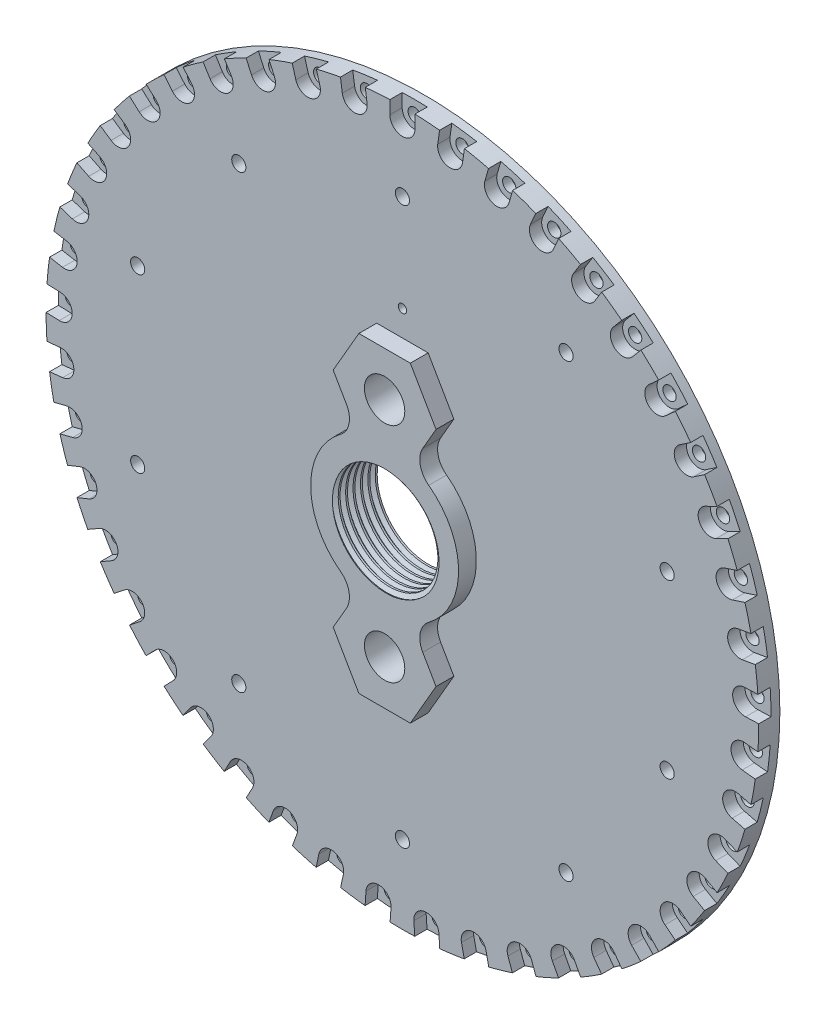
SolidWorks part; units mm, degrees
material "AISI 316 Stainless Steel Sheet (SS)"
ref_plane "Front Plane" through (0, 0, 0) normal (0, 0, 1) x (1, 0, 0)
ref_plane "Top Plane" through (0, 0, 0) normal (0, 1, 0) x (1, 0, 0)
ref_plane "Right Plane" through (0, 0, 0) normal (1, 0, 0) x (0, 0, -1)
sketch "Sketch1" plane through (0, 0, 0) normal (1, 0, 0) x (0, 0, -1)
  line L0 (0, 21.082) -> (0, 101.6)
  line L1 (0, 101.6) -> (6.0325, 101.6)
  line L2 (6.0325, 101.6) -> (6.0325, 95.25)
  line L4 (5.08, 95.25) -> (5.08, 56.8325)
  line L5 (5.08, 56.8325) -> (7.62, 56.8325)
  line L6 (7.62, 56.8325) -> (7.62, 53.0225)
  line L7 (7.62, 14.732) -> (-5.08, 14.732)
  line L8 (-5.08, 14.732) -> (-5.08, 21.082)
  line L9 (-5.08, 21.082) -> (0, 21.082)
  line L10 (0, 0) -> (59.2702, 0) construction
  line L12 (7.62, 49.6951) -> (6.2992, 49.6951)
  line L14 (7.62, 47.0535) -> (6.2992, 47.0535)
  line L15 (6.2992, 49.6951) -> (6.2992, 47.0535)
  line L20 (7.62, 47.0535) -> (7.62, 46.0375)
  line L22 (7.62, 50.4825) -> (7.62, 49.6951)
  line L23 (7.62, 21.59) -> (7.62, 14.732)
  line L24 (7.62, 46.0375) -> (5.08, 46.0375)
  line L26 (7.62, 21.59) -> (5.08, 21.59)
  line L27 (5.08, 46.0375) -> (5.08, 21.59)
  line L28 (7.62, 53.0225) -> (6.35, 53.0225)
  line L29 (6.0325, 95.25) -> (5.08, 95.25)
  line L32 (7.62, 50.4825) -> (6.35, 50.4825)
  line L33 (6.35, 53.0225) -> (6.35, 50.4825)
  point P19 (6.35, 51.7525)
  point P22 (6.2992, 48.3743)
  dimension "D1" = 203.2
  dimension "D6" = 12.7
  dimension "D8" = 6.35
  dimension "D10" = 96.7486
  dimension "D9" = 2.6416
  dimension "D11" = 1.3208
  dimension "D7" = 29.464
  dimension "D4" = 2.54
  dimension "D14" = 43.18
  dimension "D2" = 2.54
  dimension "D3" = 7.62
  dimension "D5" = 113.665
  dimension "D13" = 92.075
  dimension "D15" = 1.27
  dimension "D16" = 2.54
  dimension "D17" = 103.505
  dimension "D12" = 1.5875
  dimension "D18" = 6.35
revolve "Revolve1" add sketch "Sketch1" angle 360 about L10 region at (0, 54.5313, -2.5312)
thread "Thread1" pitch 2.1167 method cut profile "Thread Profile1" start angle 0, offset 4.318, length 0, pitch 2.1167, diameter 29.464
ref_plane "Plane1" through (-14.732, 0, 9.398) normal (0, -1, 0) x (-1, 0, 0)
sketch "Thread Profile1" plane through (-14.732, 0, 9.398) normal (0, -1, 0) x (-1, 0, 0)
  line L0 (0, 0) -> (0, 2.1167) construction
  line L1 (0, 0) -> (1.1457, 0.6615)
  line L2 (1.1457, 0.6615) -> (1.1457, 0.926)
  line L3 (1.1457, 0.926) -> (0, 1.5875)
  line L4 (1.1457, 0.7937) -> (0, 0.7937) construction
  line L11 (0, 0) -> (0, 1.5875)
  point P2 (0, 0)
  dimension "Pitch" = 2.1167
  dimension "Profile_Angle" = 60
  dimension "Profile_Land" = 0.2646
  dimension "Profile_Height" = 1.1457
sketch "Sketch15" plane through (0, 0, 0) normal (0, 0, 1) x (1, 0, 0)
  line L10 (0, 0) -> (104.8126, 0) construction
  line L11 (7.3323, 19.05) -> (14.6647, 31.75)
  line L12 (14.6647, 31.75) -> (7.3323, 44.45)
  line L13 (7.3323, 44.45) -> (-7.3323, 44.45)
  line L14 (-7.3323, 44.45) -> (-14.6647, 31.75)
  line L15 (-14.6647, 31.75) -> (-7.3323, 19.05)
  line L16 (-7.3323, 19.05) -> (7.3323, 19.05)
  line L17 (-7.3323, -19.05) -> (7.3323, -19.05)
  line L18 (-14.6647, -31.75) -> (-7.3323, -19.05)
  line L19 (-7.3323, -44.45) -> (-14.6647, -31.75)
  line L20 (7.3323, -44.45) -> (-7.3323, -44.45)
  line L21 (14.6647, -31.75) -> (7.3323, -44.45)
  line L22 (7.3323, -19.05) -> (14.6647, -31.75)
  circle A8 centre (0, 31.75) radius 12.7 construction
  circle A9 centre (0, -31.75) radius 12.7 construction
  dimension "D2" = 63.5
  dimension "D1" = 25.4
extrude "Boss-Extrude1" add sketch "Sketch15" along normal up to surface (5.08 mm away) up to face at (21.082, 0, 5.08)
hole_wizard "1/2-20 Tapped Hole2" positions "Sketch20" profile "Sketch17" tap size "1/2-20" standard "ANSI Inch" end condition through all
sketch "Sketch20" plane through (0, 0, 5.08) normal (0, 0, 1) x (1, 0, 0)
  point P9 (0, 31.75)
  point P16 (0, -31.75)
sketch "Sketch17" plane through (0, 31.75, 5.08) normal (1, 0, 0) x (0, -1, 0)
  line L0 (0, 0) -> (0, 13.4424)
  line L1 (0, 13.4424) -> (5.7544, 13.4424)
  line L2 (5.7544, 13.4424) -> (5.7544, 0)
  line L5 (5.7544, 0) -> (0, 0)
  line L11 (0, -6.35) -> (0, 107.95) construction
  dimension "Thru Tap Drill Dia." = 11.5087
  dimension "Thru Tap Drill Depth" = 13.4424
cosmetic thread "Hole Thread3" parameters "D2"=12.7
cosmetic thread "Hole Thread4" parameters "D2"=12.7
hole_wizard "CBORE for #6 Socket Head Cap Screw1" positions "Sketch31" profile "Sketch9" counterbore size "#6" standard "ANSI Inch" end condition up to next
sketch "Sketch31" [suppressed] plane through (0, 0, 0) normal (0, 0, 1) x (1, 0, 0)
  circle A0 centre (0, 0) radius 97.79 construction
  point P0 (0, 97.79)
  point P16 (13.6097, 96.8383)
  point P17 (26.9546, 94.0018)
  point P18 (39.7748, 89.3356)
  point P19 (51.8208, 82.9306)
  point P20 (62.8582, 74.9115)
  point P21 (72.6721, 65.4343)
  point P22 (81.0716, 54.6835)
  point P23 (87.8931, 42.8683)
  point P24 (93.0038, 30.2188)
  point P25 (96.3044, 16.9811)
  point P26 (97.7304, 3.4128)
  point P27 (97.2543, -10.2218)
  point P28 (94.8852, -23.6575)
  point P29 (90.6693, -36.6328)
  point P30 (84.6886, -48.895)
  point P31 (77.0596, -60.2055)
  point P32 (67.9306, -70.3442)
  point P33 (57.4795, -79.1138)
  point P34 (45.9096, -86.3434)
  point P35 (33.4461, -91.8925)
  point P36 (20.3317, -95.6531)
  point P37 (6.8215, -97.5518)
  point P38 (-6.8215, -97.5518)
  point P39 (-20.3317, -95.6531)
  point P40 (-33.4461, -91.8925)
  point P41 (-45.9096, -86.3434)
  point P42 (-57.4795, -79.1138)
  point P43 (-67.9306, -70.3442)
  point P44 (-77.0596, -60.2055)
  point P45 (-84.6886, -48.895)
  point P46 (-90.6693, -36.6328)
  point P47 (-94.8852, -23.6575)
  point P48 (-97.2543, -10.2218)
  point P49 (-97.7304, 3.4128)
  point P50 (-96.3044, 16.9811)
  point P51 (-93.0038, 30.2188)
  point P52 (-87.8931, 42.8683)
  point P53 (-81.0716, 54.6835)
  point P54 (-72.6721, 65.4343)
  point P55 (-62.8582, 74.9115)
  point P56 (-51.8208, 82.9306)
  point P57 (-39.7748, 89.3356)
  point P58 (-26.9546, 94.0018)
  point P59 (-13.6097, 96.8383)
  dimension "D1" = 195.58
  dimension "D2" = 45
sketch "Sketch9" plane through (0, 97.79, 0) normal (1, 0, 0) x (0, -1, 0)
  line L0 (0, 0) -> (0, 6.0325)
  line L1 (0, 6.0325) -> (1.8986, 6.0325)
  line L3 (1.8986, 6.0325) -> (1.8986, 3.5052)
  line L4 (1.8986, 3.5052) -> (3.5725, 3.5052)
  line L5 (3.5725, 3.5052) -> (3.5725, 0)
  line L7 (3.5725, 0) -> (0, 0)
  line L11 (0, -6.35) -> (0, 107.95) construction
  dimension "Thru Hole Dia." = 3.7973
  dimension "Thru Hole Depth" = 6.0325
  dimension "C'Bore Dia." = 7.145
  dimension "C'Bore Depth" = 3.5052
sketch "Sketch29" plane through (0, 0, 0) normal (0, 0, 1) x (1, 0, 0)
  line L0 (3.5725, 97.79) -> (3.5725, 101.5372)
  line L1 (-3.5725, 97.79) -> (-3.5725, 101.5372)
  line L2 (17.1475, 96.3411) -> (17.669, 100.0518)
  line L3 (10.072, 97.3355) -> (10.5935, 101.0462)
  line L4 (30.3887, 93.0171) -> (31.4216, 96.6191)
  line L5 (23.5205, 94.9865) -> (24.5533, 98.5885)
  line L6 (43.0384, 87.8825) -> (44.5625, 91.3058)
  line L7 (36.5111, 90.7887) -> (38.0352, 94.2119)
  line L8 (54.8505, 81.0375) -> (56.8362, 84.2153)
  line L9 (48.7911, 84.8238) -> (50.7768, 88.0015)
  line L10 (65.5949, 72.6151) -> (68.0035, 75.4856)
  line L11 (60.1215, 77.2079) -> (62.5301, 80.0784)
  line L12 (75.0626, 62.7794) -> (77.8473, 65.2867)
  line L13 (70.2817, 68.0892) -> (73.0663, 70.5965)
  line L14 (83.0693, 51.7217) -> (86.1759, 53.8171)
  line L15 (79.0739, 57.6452) -> (82.1804, 59.7406)
  line L16 (89.4592, 39.6574) -> (92.8271, 41.3)
  line L17 (86.327, 46.0793) -> (89.6949, 47.7219)
  line L18 (94.1078, 26.8211) -> (97.6716, 27.9791)
  line L19 (91.8999, 33.6164) -> (95.4636, 34.7744)
  line L20 (96.9247, 13.4628) -> (100.615, 14.1135)
  line L21 (95.684, 20.4993) -> (99.3742, 21.15)
  line L22 (97.8551, -0.1575) -> (101.6, -0.0267)
  line L23 (97.6058, 6.9832) -> (101.3506, 7.1139)
  line L24 (96.8809, -13.7748) -> (100.6075, -14.1665)
  line L25 (97.6277, -6.6689) -> (101.3544, -7.0606)
  line L26 (94.021, -27.1239) -> (97.6568, -28.0305)
  line L27 (95.7495, -20.1912) -> (99.3854, -21.0977)
  line L28 (89.331, -39.9452) -> (92.8053, -41.3489)
  line L29 (92.0076, -33.3204) -> (95.4819, -34.7241)
  line L30 (82.9024, -51.9889) -> (86.1475, -53.8625)
  line L31 (86.4749, -45.8011) -> (89.72, -47.6747)
  line L32 (74.8601, -63.0207) -> (77.8129, -65.3277)
  line L33 (79.259, -57.3904) -> (82.2118, -59.6973)
  line L34 (65.3608, -72.8259) -> (67.9638, -75.5214)
  line L35 (70.5005, -67.8626) -> (73.1035, -70.5581)
  line L36 (54.5893, -81.2136) -> (56.7918, -84.2452)
  line L37 (60.3697, -77.0139) -> (62.5723, -80.0454)
  line L38 (42.7553, -88.0206) -> (44.5145, -91.3292)
  line L39 (49.064, -84.6663) -> (50.8232, -87.9748)
  line L40 (30.0891, -93.1144) -> (31.3707, -96.6356)
  line L41 (36.8032, -90.6707) -> (38.0848, -94.1919)
  line L42 (16.8372, -96.3958) -> (17.6163, -100.0611)
  line L43 (23.8261, -94.9103) -> (24.6052, -98.5756)
  line L44 (3.2577, -97.801) -> (3.5191, -101.539)
  line L45 (10.3853, -97.3026) -> (10.6467, -101.0406)
  line L46 (-10.3853, -97.3026) -> (-10.6467, -101.0406)
  line L47 (-3.2577, -97.801) -> (-3.5191, -101.539)
  line L48 (-23.8261, -94.9103) -> (-24.6052, -98.5756)
  line L49 (-16.8372, -96.3958) -> (-17.6163, -100.0611)
  line L50 (-36.8032, -90.6707) -> (-38.0848, -94.1919)
  line L51 (-30.0891, -93.1144) -> (-31.3707, -96.6356)
  line L52 (-49.064, -84.6663) -> (-50.8232, -87.9748)
  line L53 (-42.7553, -88.0206) -> (-44.5145, -91.3292)
  line L54 (-60.3697, -77.0139) -> (-62.5723, -80.0454)
  line L55 (-54.5893, -81.2136) -> (-56.7918, -84.2452)
  line L56 (-70.5005, -67.8626) -> (-73.1035, -70.5581)
  line L57 (-65.3608, -72.8259) -> (-67.9638, -75.5214)
  line L58 (-79.259, -57.3904) -> (-82.2118, -59.6973)
  line L59 (-74.8601, -63.0207) -> (-77.8129, -65.3277)
  line L60 (-86.4749, -45.8011) -> (-89.72, -47.6747)
  line L61 (-82.9024, -51.9889) -> (-86.1475, -53.8625)
  line L62 (-92.0076, -33.3204) -> (-95.4819, -34.7241)
  line L63 (-89.331, -39.9452) -> (-92.8053, -41.3489)
  line L64 (-95.7495, -20.1912) -> (-99.3854, -21.0977)
  line L65 (-94.021, -27.1239) -> (-97.6568, -28.0305)
  line L66 (-97.6277, -6.6689) -> (-101.3544, -7.0606)
  line L67 (-96.8809, -13.7748) -> (-100.6075, -14.1665)
  line L68 (-97.6058, 6.9832) -> (-101.3506, 7.1139)
  line L69 (-97.8551, -0.1575) -> (-101.6, -0.0267)
  line L70 (-95.684, 20.4993) -> (-99.3742, 21.15)
  line L71 (-96.9247, 13.4628) -> (-100.615, 14.1135)
  line L72 (-91.8999, 33.6164) -> (-95.4636, 34.7744)
  line L73 (-94.1078, 26.8211) -> (-97.6716, 27.9791)
  line L74 (-86.327, 46.0793) -> (-89.6949, 47.7219)
  line L75 (-89.4592, 39.6574) -> (-92.8271, 41.3)
  line L76 (-79.0739, 57.6452) -> (-82.1804, 59.7406)
  line L77 (-83.0693, 51.7217) -> (-86.1759, 53.8171)
  line L78 (-70.2817, 68.0892) -> (-73.0663, 70.5965)
  line L79 (-75.0626, 62.7794) -> (-77.8473, 65.2867)
  line L80 (-60.1215, 77.2079) -> (-62.5301, 80.0784)
  line L81 (-65.5949, 72.6151) -> (-68.0035, 75.4856)
  line L82 (-48.7911, 84.8238) -> (-50.7768, 88.0015)
  line L83 (-54.8505, 81.0375) -> (-56.8362, 84.2153)
  line L84 (-36.5111, 90.7887) -> (-38.0352, 94.2119)
  line L85 (-43.0384, 87.8825) -> (-44.5625, 91.3058)
  line L86 (-23.5205, 94.9865) -> (-24.5533, 98.5885)
  line L87 (-30.3887, 93.0171) -> (-31.4216, 96.6191)
  line L88 (-10.072, 97.3355) -> (-10.5935, 101.0462)
  line L89 (-17.1475, 96.3411) -> (-17.669, 100.0518)
  circle A0 centre (0, 97.79) radius 3.5725 construction
  circle A1 centre (0, 0) radius 101.6 construction
  circle A2 centre (13.6097, 96.8383) radius 3.5725
  circle A3 centre (0, 97.79) radius 3.5725
  circle A4 centre (26.9546, 94.0018) radius 3.5725
  circle A5 centre (0, 0) radius 101.6
  circle A7 centre (39.7748, 89.3356) radius 3.5725
  circle A8 centre (51.8208, 82.9306) radius 3.5725
  circle A9 centre (62.8582, 74.9115) radius 3.5725
  circle A10 centre (72.6721, 65.4343) radius 3.5725
  circle A11 centre (81.0716, 54.6835) radius 3.5725
  circle A12 centre (87.8931, 42.8683) radius 3.5725
  circle A13 centre (93.0038, 30.2188) radius 3.5725
  circle A14 centre (96.3044, 16.9811) radius 3.5725
  circle A15 centre (97.7304, 3.4128) radius 3.5725
  circle A16 centre (97.2543, -10.2218) radius 3.5725
  circle A17 centre (94.8852, -23.6575) radius 3.5725
  circle A18 centre (90.6693, -36.6328) radius 3.5725
  circle A19 centre (84.6886, -48.895) radius 3.5725
  circle A20 centre (77.0596, -60.2055) radius 3.5725
  circle A21 centre (67.9306, -70.3442) radius 3.5725
  circle A22 centre (57.4795, -79.1138) radius 3.5725
  circle A23 centre (45.9096, -86.3434) radius 3.5725
  circle A24 centre (33.4461, -91.8925) radius 3.5725
  circle A25 centre (13.6097, 96.8383) radius 1.8986 construction
  circle A26 centre (20.3317, -95.6531) radius 3.5725
  circle A27 centre (6.8215, -97.5518) radius 3.5725
  circle A28 centre (-6.8215, -97.5518) radius 3.5725
  circle A29 centre (-20.3317, -95.6531) radius 3.5725
  circle A30 centre (-33.4461, -91.8925) radius 3.5725
  circle A31 centre (-45.9096, -86.3434) radius 3.5725
  circle A32 centre (-57.4795, -79.1138) radius 3.5725
  circle A33 centre (-67.9306, -70.3442) radius 3.5725
  circle A34 centre (-77.0596, -60.2055) radius 3.5725
  circle A35 centre (-84.6886, -48.895) radius 3.5725
  circle A36 centre (-90.6693, -36.6328) radius 3.5725
  circle A37 centre (-94.8852, -23.6575) radius 3.5725
  circle A38 centre (-97.2543, -10.2218) radius 3.5725
  circle A39 centre (-97.7304, 3.4128) radius 3.5725
  circle A40 centre (-96.3044, 16.9811) radius 3.5725
  circle A41 centre (-93.0038, 30.2188) radius 3.5725
  circle A42 centre (-87.8931, 42.8683) radius 3.5725
  circle A43 centre (-81.0716, 54.6835) radius 3.5725
  circle A44 centre (-72.6721, 65.4343) radius 3.5725
  circle A45 centre (-62.8582, 74.9115) radius 3.5725
  circle A46 centre (-51.8208, 82.9306) radius 3.5725
  circle A47 centre (-39.7748, 89.3356) radius 3.5725
  circle A48 centre (-26.9546, 94.0018) radius 3.5725
  circle A49 centre (-13.6097, 96.8383) radius 3.5725
  circle A51 centre (0, 0) radius 101.6
  point P129 (0, 0)
  dimension "D2" = 45
extrude "Cut-Extrude1" cut sketch "Sketch29" against normal up to surface (3.5052 mm away) contours L1 L0 region at (0, 101.4435, 0) up to face at (1.8986, 97.79, -3.5052)
pattern_circular "CirPattern2" count 45 over 360 about axis through (0, 0, 0) along (0, 0, 1) of "Cut-Extrude1"
fillet "Fillet1" radius 6.35 4 edges at (-7.6711, 19.6368, 2.54) (-7.6711, -19.6368, 2.54) (7.6711, -19.6368, 2.54) (7.6711, 19.6368, 2.54)
hole_wizard "3/32 (0.09375) Dowel Hole1" positions "Sketch23" profile "Sketch22" hole size "3/32" standard "ANSI Inch" end condition up to next
sketch "Sketch23" plane through (0, 0, -6.35) normal (0, 0, -1) x (-1, 0, 0)
  line L0 (0, 50.4825) -> (0, 53.0225) construction
  circle A1 centre (0, 0) radius 50.4825 construction
  circle A2 centre (0, 0) radius 53.0225 construction
  point P0 (0, 51.7525)
  point P15 (0, 51.7525)
sketch "Sketch22" plane through (0, 51.7525, -6.35) normal (1, 0, 0) x (0, 1, 0)
  line L0 (0, 0) -> (0, 6.35)
  line L1 (0, 6.35) -> (1.1906, 6.35)
  line L2 (1.1906, 6.35) -> (1.1906, 0)
  line L5 (1.1906, 0) -> (0, 0)
  line L11 (0, -6.35) -> (0, 107.95) construction
  dimension "Thru Hole Dia." = 2.3812
  dimension "Thru Hole Depth" = 6.35
sketch "Sketch24" plane through (0, 0, 0) normal (0, 0, 1) x (1, 0, 0)
  line L0 (0, 56.8325) -> (0, 101.9175) construction
  line L2 (6.8215, 97.5518) -> (0, 0) construction
  circle A0 centre (0, 0) radius 79.375 construction
  circle A1 centre (0, 0) radius 56.8325 construction
  circle A2 centre (0, 0) radius 56.8325 construction
  arc A4 (0, 97.79) -> (13.6097, 96.8383) centre (0, 0) cw construction
  arc A6 (10.072, 97.3355) -> (17.1475, 96.3411) centre (13.6097, 96.8383) ccw construction
  point P0 (0, 79.375)
  point P14 (0, 79.375)
  dimension "D1" = 158.75
sketch "Sketch32" plane through (0, 0, 0) normal (0, 0, 1) x (1, 0, 0)
  point P0 (0, 79.375)
  point P4 (0, 0)
hole_wizard "#10-32 Tapped Hole1" positions "Sketch32" profile "Sketch27" tap size "#10-32" standard "ANSI Inch"
sketch "Sketch27" plane through (0, 79.375, 0) normal (1, 0, 0) x (0, -1, 0)
  line L0 (0, 0) -> (0, 4.318)
  line L1 (0, 4.318) -> (2.0193, 3.1047)
  line L2 (2.0193, 3.1047) -> (2.0193, 0)
  line L5 (2.0193, 0) -> (0, 0)
  line L10 (0, 4.318) -> (-2.0193, 3.1047) construction
  line L11 (0, -6.35) -> (0, 107.95) construction
  dimension "Tap Drill Dia." = 4.0386
  dimension "Tap Drill Depth" = 4.318
  dimension "Drill Angle" = 118
cosmetic thread "Hole Thread5" parameters "D1"=9.652, "D2"=4.826
pattern_circular "CirPattern1" count 10 over 360 about axis through (0, 0, 0) along (0, 0, 1) of "#10-32 Tapped Hole1" reverse direction yes
cosmetic thread "Hole Thread6" parameters "D1"=9.652, "D2"=4.826
cosmetic thread "Hole Thread7" parameters "D1"=9.652, "D2"=4.826
cosmetic thread "Hole Thread8" parameters "D1"=9.652, "D2"=4.826
cosmetic thread "Hole Thread9" parameters "D1"=9.652, "D2"=4.826
cosmetic thread "Hole Thread10" parameters "D1"=9.652, "D2"=4.826
cosmetic thread "Hole Thread11" parameters "D1"=9.652, "D2"=4.826
cosmetic thread "Hole Thread12" parameters "D1"=9.652, "D2"=4.826
cosmetic thread "Hole Thread13" parameters "D1"=9.652, "D2"=4.826
cosmetic thread "Hole Thread14" parameters "D1"=9.652, "D2"=4.826
equation "\"numBolts\"= 45"
equation "\"chamberOD\"= 8"
equation "\"boltDia\"= 7.7"
equation "\"D1@Sketch1\"=\"chamberOD\""
equation "\"D1@Sketch31\" = \"boltDia\""
equation "\"D2@Sketch31\" = \"numBolts\""
equation "\"D2@Sketch29\"=\"numBolts\""
equation "\"D1@CirPattern2\"=\"numBolts\""
